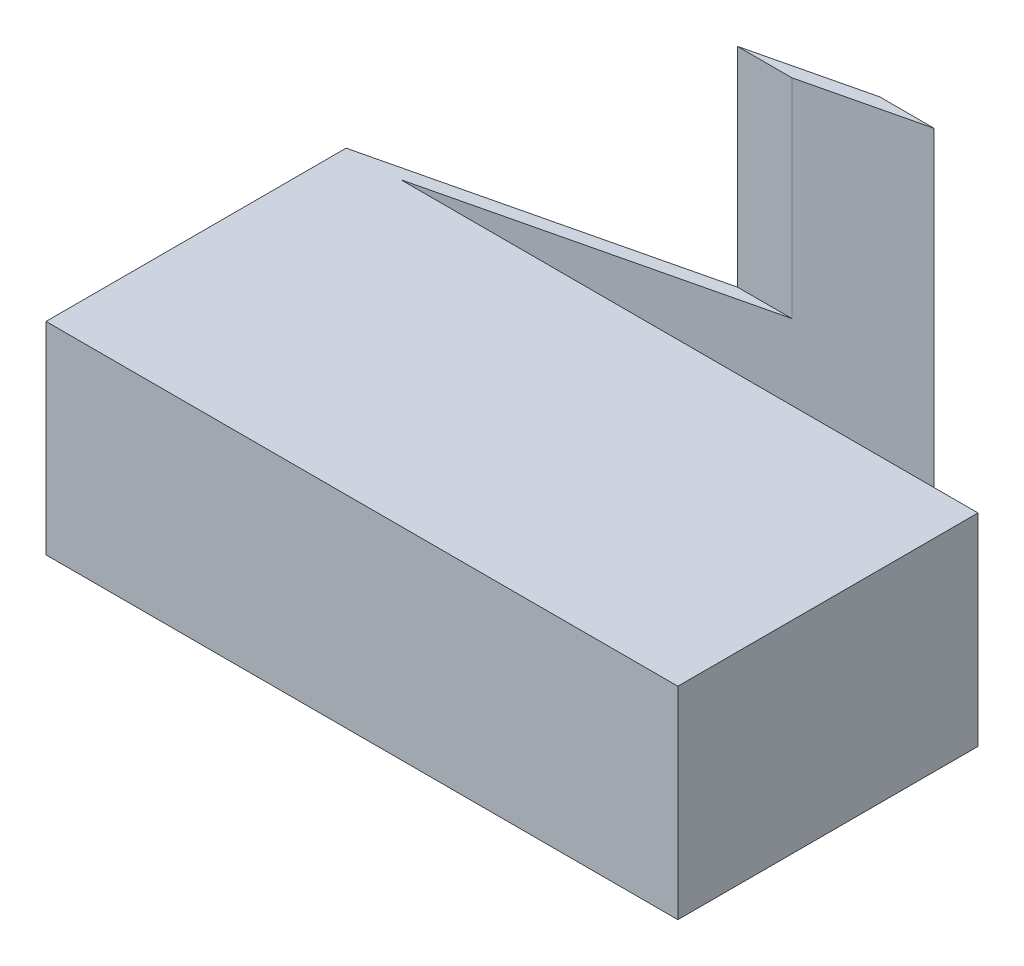
SolidWorks part; units mm, degrees
ref_plane "Ebene vorne" through (0, 0, 0) normal (0, 0, 1) x (1, 0, 0)
ref_plane "Ebene oben" through (0, 0, 0) normal (0, 1, 0) x (1, 0, 0)
ref_plane "Ebene rechts" through (0, 0, 0) normal (1, 0, 0) x (0, 0, -1)
sketch "Skizze1" plane through (0, 0, 0) normal (0, 1, 0) x (1, 0, 0)
  line L0 (-10, 4.75) -> (-8.2746, 4.75)
  line L1 (-10, 4.75) -> (10, 4.75)
  line L2 (-10, 4.75) -> (-10, -4.75)
  line L3 (-10, -4.75) -> (10, -4.75)
  line L4 (10, 4.75) -> (10, -4.75)
  line L5 (-10, 4.75) -> (3.6373, 8)
  line L6 (-8.2746, 4.75) -> (5.3627, 8)
  line L7 (3.6373, 8) -> (5.3627, 8)
  line L8 (0, 7.1332) -> (1.7254, 7.1332)
  point P4 (0, -4.75)
  point P6 (-10, 0)
  point P7 (4.5, 8)
  point P13 (1.6161, 7.1332)
  dimension "D1" = 20
  dimension "D2" = 9.5
  dimension "D3" = 0.4
  dimension "D4" = 14.5
  dimension "D5" = 3.25
extrude "Aufsatz-Linear austragen1" add sketch "Skizze1" along normal blind 6.4 contours L7 L5 L0 L6 | L0 L5 L7 L6 | L2 L1 L4 L3 region at (-4.1373, 0, -5.9416)
extrude "Aufsatz-Linear austragen2" add sketch "Skizze1<3>" along normal blind 13 contours L5 L8 L6 L7 region at (2.6814, 0, -7.5666)
sketch "Skizze1<3>" plane through (0, 0, 0) normal (0, 1, 0) x (1, 0, 0) same geometry as "Skizze1"
